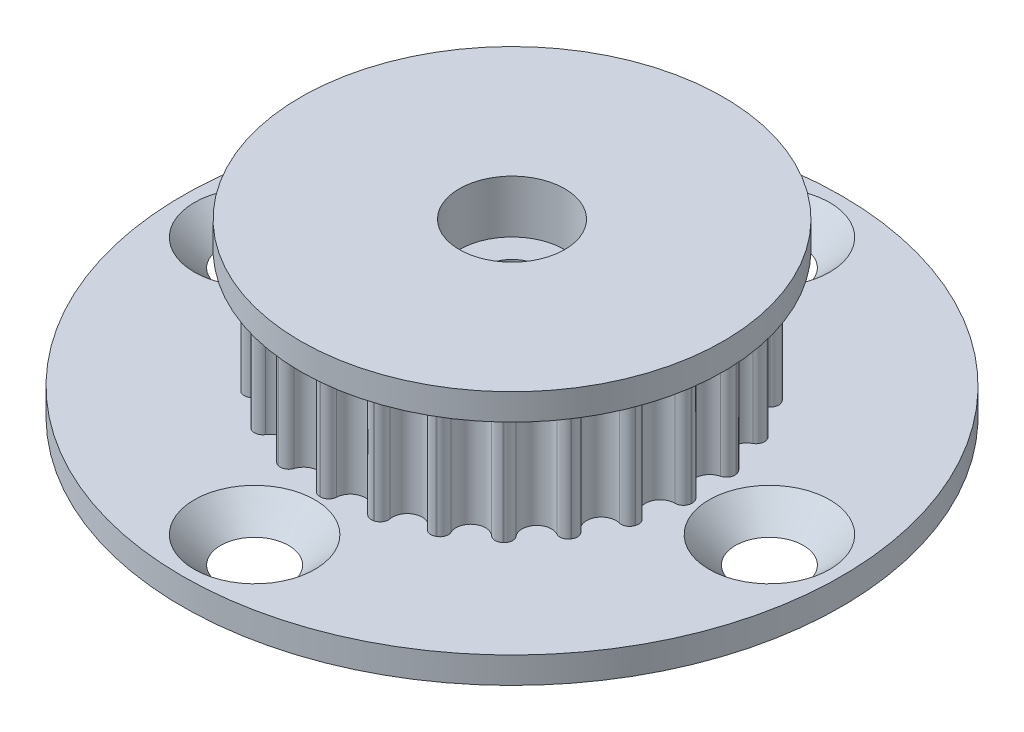
SolidWorks part; units mm, degrees
ref_plane "Front Plane" through (0, 0, 0) normal (0, 0, 1) x (1, 0, 0)
ref_plane "Top Plane" through (0, 0, 0) normal (0, 1, 0) x (1, 0, 0)
ref_plane "Right Plane" through (0, 0, 0) normal (1, 0, 0) x (0, 0, -1)
sketch "Sketch1" plane through (0, 0, 0) normal (0, 1, 0) x (1, 0, 0)
  line L0 (0, 0) -> (0, 11.5556) construction
  line L1 (0, 0) -> (2.7917, 10.8729) construction
  circle A0 centre (0, 0) radius 11.5556 construction
  circle A1 centre (0, 0) radius 10.3356 construction
  circle A2 centre (0, 11.2256) radius 0.89 construction
  circle A5 centre (2.7917, 10.8729) radius 0.89 construction
  arc A6 (0, 10.3356) -> (0.8749, 11.0624) centre (0, 11.2256) ccw
  arc A7 (0.8749, 11.0624) -> (1.4283, 11.467) centre (1.3665, 10.9708) cw
  arc A8 (1.4683, 11.4619) -> (1.9037, 10.9325) centre (1.4048, 10.9659) cw
  arc A9 (2.5703, 10.0109) -> (1.9037, 10.9325) centre (2.7917, 10.8729) cw
  arc A10 (1.4283, 11.467) -> (1.4683, 11.4619) centre (0, 0) cw
  arc A11 (0, 10.3356) -> (2.5703, 10.0109) centre (0, 0) ccw
  dimension "D1" = 23.1111
  dimension "D3" = 1.78
  dimension "D4" = 0.5
  dimension "D2" = 1.22
  dimension "D5" = 14.4
extrude "Boss-Extrude1" add sketch "Sketch1" along normal mid plane 7.112
ref_axis "Axis1" through (0, 3.3, 0) along (0, -1, 0)
pattern_circular "CirPattern1" count 25 over 360 about axis through (0, 3.3, 0) along (0, -1, 0) of "Boss-Extrude1"
sketch "Sketch2" plane through (0, 0, 0) normal (1, 0, 0) x (0, 0, -1)
  line L10 (0, 3.556) -> (12.7303, 3.556) construction
  line L11 (0, 3.556) -> (0, 5.1435) construction
  line L12 (0, 5.1435) -> (12.7303, 5.1435) construction
  line L15 (12.7303, 3.556) -> (12.7303, 5.1435) construction
  line L20 (0, 3.3) -> (0, -3.3) construction
  line L22 (12.7303, 5.1435) -> (0, 5.1435)
  line L23 (12.7303, 5.1435) -> (12.7303, 3.556)
  line L24 (12.7303, 3.556) -> (0, 3.556)
  line L25 (0, 5.1435) -> (0, 3.556)
  line L26 (-11.0849, 3.556) -> (-11.5555, 3.556) construction
  dimension "D1" = 1.5875
  dimension "D2" = 12.7303
revolve "Revolve3" add sketch "Sketch2" angle 360 about axis through (0, 3.3, 0) along (0, -1, 0) region at (0, 4.3497, -6.3652)
mirror "Mirror1" about plane through (0, 0, 0) normal (0, 1, 0) of "Revolve3"
sketch "Sketch9" plane through (0, -5.1435, 0) normal (0, -1, 0) x (1, 0, 0)
  circle A0 centre (0, 0) radius 19.8438
  circle A1 centre (0, 0) radius 1.5
  dimension "D1" = 3
  dimension "D2" = 39.6875
extrude "Boss-Extrude2" add sketch "Sketch9" against normal up to surface (1.5875 mm away) up to face at (0, -3.556, 0)
sketch "Sketch3" plane through (0, 0, 0) normal (0, 1, 0) x (1, 0, 0)
  circle A0 centre (-15.5, 0) radius 1.7462
  circle A3 centre (0, 15.5) radius 1.7462
  circle A4 centre (15.5, 0) radius 1.7463
  circle A5 centre (0, -15.5) radius 1.7462
  dimension "D3" = 3.4925
  dimension "D1" = 15.5
  dimension "D4" = 4
extrude "Cut-Extrude1" cut sketch "Sketch3" against normal through all both and the other way through all
ref_axis "Axis2" through (-15.5, -5.1435, 0) along (0, 1, 0)
sketch "Sketch6" plane through (0, 0, 0) normal (0, 0, 1) x (1, 0, 0)
  line L0 (-19.1322, -3.556) -> (-11.8678, -3.556) construction
  line L1 (-13.7538, -3.556) -> (-17.2462, -3.556) construction
  line L2 (-11.8678, -3.556) -> (-15.5, -7.1882)
  line L3 (-15.5, -7.1882) -> (-19.1322, -3.556) construction
  line L4 (-18.548, -4.1402) -> (-12.452, -4.1402) construction
  line L5 (-17.2462, -3.998) -> (-13.7538, -3.998) construction
  line L8 (-15.5, -7.1882) -> (-15.5, -3.556)
  line L9 (-15.5, -3.556) -> (-11.8678, -3.556)
  line L10 (-15.5, -5.1435) -> (-15.5, -3.556) construction
  line L12 (-17.2462, -3.556) -> (-17.2462, -5.1435) construction
  line L13 (-13.7538, -5.1435) -> (-13.7538, -3.556) construction
  point P2 (-15.5, -3.998)
  point P7 (-12.452, -3.8707)
  dimension "D1" = 6.096
  dimension "D2" = 0.5842
revolve "Cut-Revolve2" cut sketch "Sketch6" angle 360 about axis through (-15.5, -5.1435, 0) along (0, 1, 0)
pattern_circular "CirPattern2" count 4 over 360 about axis through (0, 3.3, 0) along (0, -1, 0) of "Cut-Revolve2"
sketch "Sketch12" plane through (0, 5.1435, 0) normal (0, 1, 0) x (1, 0, 0)
  circle A0 centre (0, 0) radius 3.175
  dimension "D1" = 6.35
extrude "Cut-Extrude2" cut sketch "Sketch12" against normal blind 3.175 from surface starting at face at (0, 5.1435, 12.7303)
sketch "Sketch13" plane through (0, 1.9685, 0) normal (0, 1, 0) x (1, 0, 0)
  circle A0 centre (0, 0) radius 1.525
  dimension "D1" = 3.05
extrude "Cut-Extrude4" cut sketch "Sketch13" against normal through all contours A0
equation "\"TEETH_NUM\"= 25"
equation "\"TOOTH_PITCH\"= 3mm"
equation "\"PITCH_LINE_OFFSET\"= .015in"
equation "\"DIAMETER_PER_GROOVE\"= .954925mm"
equation "\"PITCH_DIAMETER\"= \"TEETH_NUM\" * \"DIAMETER_PER_GROOVE\""
equation "\"OUTSIDE_DIAMETER\"= \"PITCH_DIAMETER\" - \"PITCH_LINE_OFFSET\" * 2"
equation "\"D1@Sketch1\"=\"OUTSIDE_DIAMETER\""
equation "\"TOOTH_HEIGHT\"= 1.22mm"
equation "\"D2@Sketch1\"=\"TOOTH_HEIGHT\""
equation "\"TOOTH_DIAMETER\"= 1.78mm"
equation "\"INTERNAL_RADIUS\"= .5mm"
equation "\"D3@Sketch1\"=\"TOOTH_DIAMETER\""
equation "\"D5@Sketch1\"=360 / \"TEETH_NUM\""
equation "\"D4@Sketch1\"=\"INTERNAL_RADIUS\""
equation "\"D1@CirPattern1\"=\"TEETH_NUM\""
equation "\"BELT_GAP\"= 7mm"
equation "\"D2@Sketch2\"=\"PITCH_DIAMETER\"/2+1/32"
